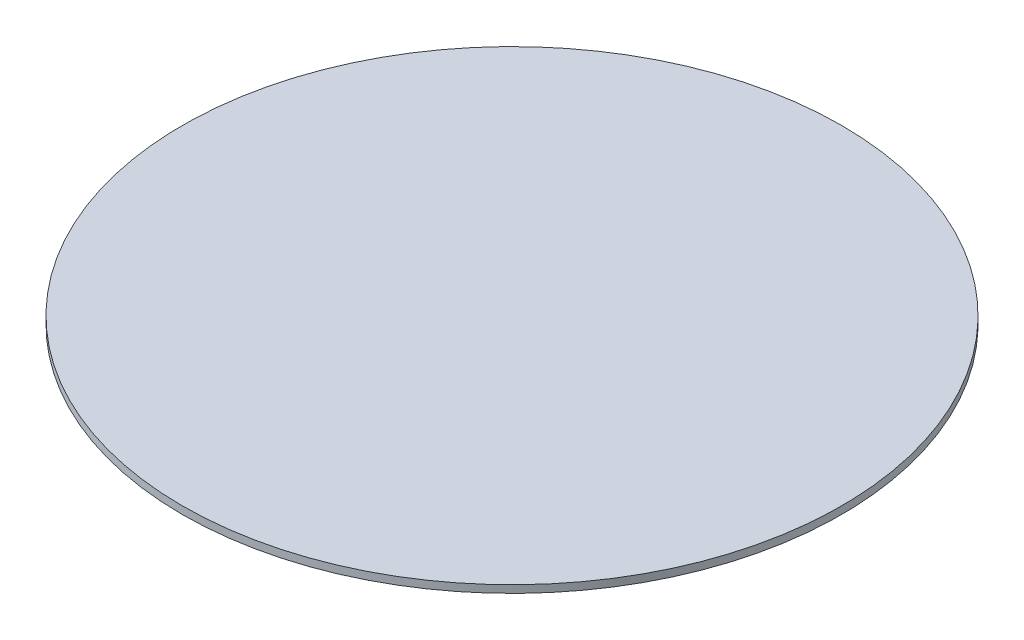
SolidWorks part; units mm, degrees
ref_plane "Front Plane" through (0, 0, 0) normal (0, 0, 1) x (1, 0, 0)
ref_plane "Top Plane" through (0, 0, 0) normal (0, 1, 0) x (1, 0, 0)
ref_plane "Right Plane" through (0, 0, 0) normal (1, 0, 0) x (0, 0, -1)
sketch "Sketch1" plane through (0, 0, 0) normal (0, 1, 0) x (1, 0, 0)
  circle A0 centre (0, 0) radius 175
  dimension "D1" = 350
extrude "Boss-Extrude1" add sketch "Sketch1" along normal blind 4
